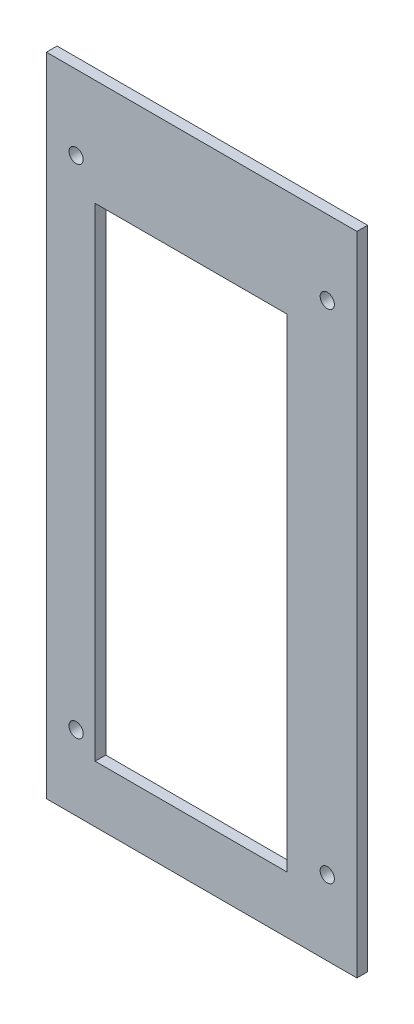
SolidWorks part; units mm, degrees
ref_plane "Front Plane" through (0, 0, 0) normal (0, 0, 1) x (1, 0, 0)
ref_plane "Top Plane" through (0, 0, 0) normal (0, 1, 0) x (1, 0, 0)
ref_plane "Right Plane" through (0, 0, 0) normal (1, 0, 0) x (0, 0, -1)
sketch "Sketch1" plane through (0, 0, 0) normal (0, 0, 1) x (1, 0, 0)
  line L0 (-17.675, 45.5) -> (-17.675, -45.5) construction
  line L1 (-21.85, 45.5) -> (21.85, 45.5)
  line L2 (-21.85, 45.5) -> (-21.85, -45.5)
  line L3 (-21.85, -45.5) -> (21.85, -45.5)
  line L4 (21.85, 45.5) -> (21.85, -45.5)
  line L5 (-21.85, 45.5) -> (21.85, -45.5) construction
  line L6 (-21.85, -45.5) -> (21.85, 45.5) construction
  line L7 (17.675, 45.5) -> (17.675, -45.5) construction
  line L8 (-15, 45.5) -> (-15, -45.5) construction
  line L9 (-15, 30.5) -> (12, 30.5)
  line L10 (-15, 30.5) -> (-15, -37.5)
  line L11 (-15, -37.5) -> (12, -37.5)
  line L12 (12, 30.5) -> (12, -37.5)
  line L13 (-20.35, -45.5) -> (-20.35, 45.5) construction
  line L14 (15, 45.5) -> (15, -45.5) construction
  line L15 (20.35, -45.5) -> (20.35, 45.5) construction
  line L16 (-21, 11.5) -> (21, 11.5) construction
  line L17 (-21.85, 0) -> (21.85, 0) construction
  line L18 (0, 45.5) -> (0, -45.5) construction
  circle A0 centre (17.675, 35) radius 1
  circle A1 centre (17.675, -35) radius 1
  circle A2 centre (-17.675, 35) radius 1
  circle A3 centre (-17.675, -35) radius 1
  point P0 (0, 0)
  dimension "D7" = 2
  dimension "D8" = 70
  dimension "D9" = 70
  dimension "D14" = 35
  dimension "D2" = 27
  dimension "D3" = 1.5
  dimension "D4" = 3
  dimension "D5" = 43.7
  dimension "D6" = 1.5
  dimension "D10" = 5.35
  dimension "D11" = 2.675
  dimension "D12" = 0
  dimension "5.65" = 5.35
  dimension "D13" = 2.675
  dimension "D15" = 19
  dimension "D16" = 49
  dimension "D17" = 15
  dimension "D18" = 10.5
  dimension "D19" = 35.35
  dimension "D20" = 91
extrude "Boss-Extrude1" add sketch "Sketch1" along normal blind 1.5
